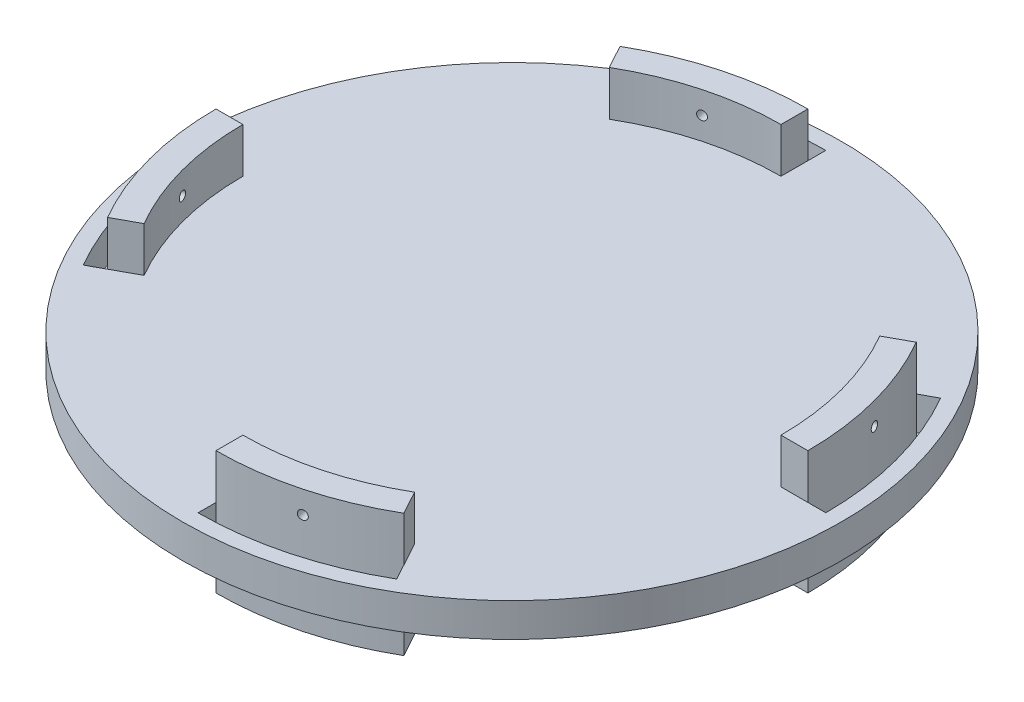
SolidWorks part; units mm, degrees
material "6061-T6 (SS)"
ref_plane "Front Plane" through (0, 0, 0) normal (0, 0, 1) x (1, 0, 0)
ref_plane "Top Plane" through (0, 0, 0) normal (0, 1, 0) x (1, 0, 0)
ref_plane "Right Plane" through (0, 0, 0) normal (1, 0, 0) x (0, 0, -1)
sketch "Sketch1" plane through (0, 0, 0) normal (0, 1, 0) x (1, 0, 0)
  circle A0 centre (0, 0) radius 93.345
  dimension "D1" = 186.69
extrude "Base" add sketch "Sketch1" along normal blind 4.7625 and the other way blind 4.7625
sketch "Sketch2" plane through (0, 4.7625, 0) normal (0, 1, 0) x (1, 0, 0)
  line L0 (0, 0) -> (0, 93.345) construction
  line L1 (-55, 0) -> (55, 0) construction
  line L2 (0, 88.9) -> (0, 83.82)
  line L3 (-41.9567, 72.5633) -> (-44.3929, 77.0226)
  line L4 (0, 0) -> (0, 93.345) construction
  arc A0 (-41.9567, 72.5633) -> (0, 83.82) centre (0, 0) cw
  arc A1 (-44.3929, 77.0226) -> (0, 88.9) centre (0, 0) cw
  circle A8 centre (0, 0) radius 93.345 construction
  dimension "D1" = 83.82
  dimension "D3" = 43.942
  dimension "D4" = 46.482
  dimension "D2" = 88.9
extrude "Bottom support holes" cut sketch "Sketch2" against normal blind 4.7625
sketch "Sketch3" plane through (0, 4.7625, 0) normal (0, 1, 0) x (1, 0, 0)
  line L0 (0, 0) -> (0, 93.345) construction
  line L2 (0, 83.82) -> (0, 76.2)
  line L3 (-38.3023, 65.8739) -> (-41.9567, 72.5633)
  line L4 (-5.2388, 0) -> (5.2388, 0) construction
  line L7 (-44.3929, 77.0226) -> (-41.9567, 72.5633) construction
  arc A0 (-38.3023, 65.8739) -> (0, 76.2) centre (0, 0) cw
  arc A1 (-41.9567, 72.5633) -> (0, 83.82) centre (0, 0) cw
  circle A2 centre (0, 0) radius 93.345 construction
  dimension "D1" = 76.2
  dimension "D4" = 43.942
  dimension "D2" = 83.82
extrude "Bottom support guide" add sketch "Sketch3" along normal blind 12.7
ref_plane "Bottom bolt hole plane" through (-20.9784, 0, -78.1916) normal (-0.2591, 0, -0.9658) x (-0.9658, 0, 0.2591)
sketch "Sketch6" plane through (-20.9784, 0, -78.1916) normal (-0.2591, 0, -0.9658) x (-0.9658, 0, 0.2591)
  line L0 (22.9177, 4.7625) -> (-23.0366, 4.7625) construction
  line L1 (-21.7203, 4.7625) -> (-21.7203, 17.4625) construction
  circle A0 centre (-0.0033, 11.1125) radius 1.27
  dimension "D1" = 2.54
  dimension "D2" = 6.35
  dimension "D3" = 21.717
extrude "Bottom bolt hole" cut sketch "Sketch6" against normal blind 12.7 and the other way blind 12.7
mirror "Support mirror" about plane through (0, 0, 0) normal (0, 1, 0) of "Bottom support guide", "Bottom bolt hole", "Bottom support holes"
pattern_circular "Bottom pattern" count 4 over 360 about axis through (0, 4.7625, 0) along (0, 1, 0) of "Bottom support holes", "Bottom support guide", "Bottom bolt hole", "Support mirror"
sketch "Sketch8" plane through (-31.123, 4.7625, 77.2967) normal (0, 1, 0) x (1, 0, 0)
  line L0 (31.123, 77.2967) -> (-34.8819, 143.3016) construction
  line L2 (-31.7388, 140.1585) -> (-28.1467, 136.5664)
  line L3 (-49.8549, 98.9388) -> (-54.7307, 100.3694)
  line L4 (31.123, 77.2967) -> (-34.8819, 143.3016) construction
  line L5 (31.123, 77.2967) -> (31.123, 170.6417) construction
  arc A0 (-49.8549, 98.9388) -> (-28.1467, 136.5664) centre (31.123, 77.2967) cw
  arc A1 (-54.7307, 100.3694) -> (-31.7388, 140.1585) centre (31.123, 77.2967) cw
  circle A3 centre (31.123, 77.2967) radius 93.345 construction
  dimension "D1" = 83.82
  dimension "D3" = 43.942
  dimension "D4" = 46.482
  dimension "D2" = 88.9
  dimension "D5" = 45
extrude "Top support holes" [suppressed] cut sketch "Sketch8" against normal blind 4.7625
sketch "Sketch10" [suppressed] plane through (-31.123, 4.7625, 77.2967) normal (0, 1, 0) x (1, 0, 0)
  line L0 (31.123, 77.2967) -> (-34.8819, 143.3016) construction
  line L2 (-28.1467, 136.5664) -> (-22.7586, 131.1782)
  line L3 (-42.5407, 96.7928) -> (-49.8549, 98.9388)
  line L7 (-54.7307, 100.3694) -> (-49.8549, 98.9388) construction
  arc A0 (-42.5407, 96.7928) -> (-22.7586, 131.1782) centre (31.123, 77.2967) cw
  arc A1 (-49.8549, 98.9388) -> (-28.1467, 136.5664) centre (31.123, 77.2967) cw
  dimension "D1" = 76.2
  dimension "D4" = 43.942
  dimension "D2" = 83.82
extrude "Top support guide" [suppressed] add sketch "Sketch10" along normal blind 12.7
ref_plane "Top bolt hole plane" [suppressed] through (-70.1238, 0, -40.4559) normal (-0.8662, 0, -0.4997) x (-0.4997, 0, 0.8662)
sketch "Sketch12" [suppressed] plane through (-70.1238, 0, -40.4559) normal (-0.8662, 0, -0.4997) x (-0.4997, 0, 0.8662)
  line L0 (22.9177, 4.7625) -> (-23.0366, 4.7625) construction
  line L1 (-21.7203, 4.7625) -> (-21.7203, 17.4625) construction
  circle A0 centre (-0.0033, 11.1125) radius 1.27
  dimension "D1" = 2.54
  dimension "D2" = 6.35
  dimension "D3" = 21.717
extrude "Top bolt hole" [suppressed] cut sketch "Sketch12" against normal blind 12.7 and the other way blind 12.7
pattern_circular "CirPattern3" [suppressed] count 4 over 360 of bodies 109
